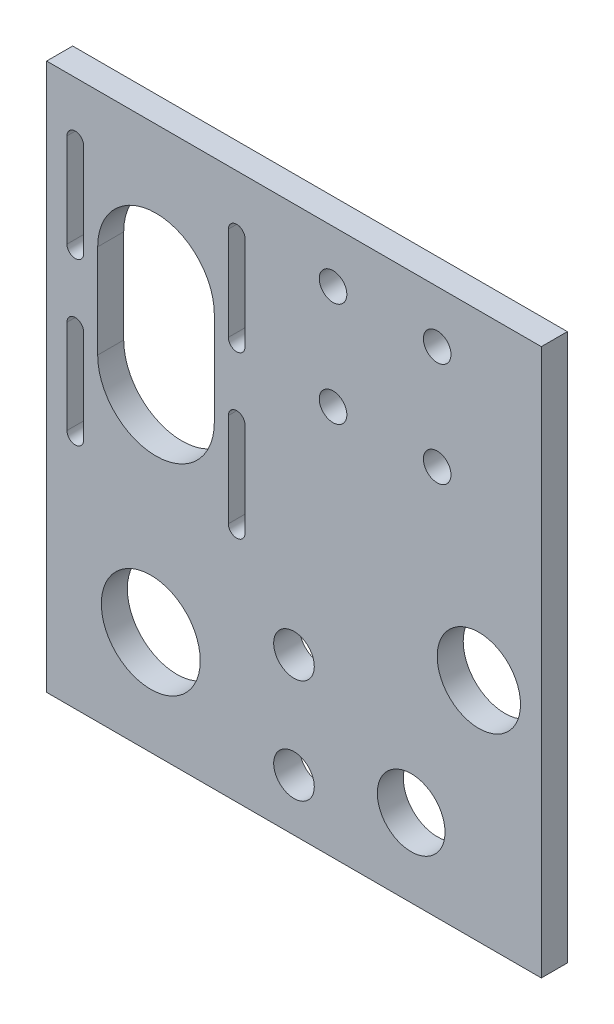
SolidWorks part; units mm, degrees
material "5052-O"
ref_plane "前基準面" through (0, 0, 0) normal (0, 0, 1) x (1, 0, 0)
ref_plane "上基準面" through (0, 0, 0) normal (0, 1, 0) x (1, 0, 0)
ref_plane "右基準面" through (0, 0, 0) normal (1, 0, 0) x (0, 0, -1)
sketch "草圖1" plane through (0, 0, 0) normal (0, 0, 1) x (1, 0, 0)
  line L1 (-47.5, -37.5) -> (47.5, -37.5)
  line L2 (-47.5, -37.5) -> (-47.5, 37.5)
  line L3 (-47.5, 37.5) -> (47.5, 37.5)
  line L4 (47.5, -37.5) -> (47.5, 37.5)
  line L5 (-47.5, -37.5) -> (47.5, 37.5) construction
  line L6 (-47.5, 37.5) -> (47.5, -37.5) construction
  point P0 (0, 0)
  dimension "D1" = 95
  dimension "D2" = 75
extrude "填料-伸長1" add sketch "草圖1" along normal blind 5
hole_wizard "M5 餘隙孔1" positions "草圖2" profile "草圖3" hole size "M5" standard "Ansi Metric" end condition through all
sketch "草圖2" plane through (0, 0, 5) normal (0, 0, 1) x (1, 0, 0)
  line L3 (7.5, 7.5) -> (27.5, 7.5) construction
  line L4 (7.5, 7.5) -> (7.5, 27.5) construction
  line L5 (7.5, 27.5) -> (27.5, 27.5) construction
  line L6 (27.5, 7.5) -> (27.5, 27.5) construction
  line L7 (7.5, 7.5) -> (27.5, 27.5) construction
  line L8 (7.5, 27.5) -> (27.5, 7.5) construction
  line L11 (47.5, 37.5) -> (-47.5, 37.5) construction
  line L12 (47.5, -37.5) -> (47.5, 37.5) construction
  point P6 (27.5, 27.5)
  point P15 (7.5, 7.5)
  point P16 (7.5, 27.5)
  point P17 (27.5, 7.5)
  point P35 (17.5, 17.5)
  dimension "D1" = 20
  dimension "D2" = 20
  dimension "D3" = 20
  dimension "D4" = 20
sketch "草圖3" plane through (27.5, 27.5, 5) normal (1, 0, 0) x (0, -1, 0)
  line L0 (0, 0) -> (0, 5)
  line L1 (0, 5) -> (2.65, 5)
  line L2 (2.65, 5) -> (2.65, 0)
  line L5 (2.65, 0) -> (0, 0)
  line L11 (0, -6.35) -> (0, 107.95) construction
  dimension "貫穿孔直徑" = 5.3
  dimension "貫穿孔深度" = 5
sketch "草圖6" plane through (0, 0, 5) normal (0, 0, 1) x (1, 0, 0)
  line L0 (47.5, 37.5) -> (-47.5, 37.5) construction
  line L2 (-26.5, -6.5) -> (-26.5, 11.5) construction
  line L3 (-37.7, -6.5) -> (-37.7, 11.5)
  line L4 (-15.3, -6.5) -> (-15.3, 11.5)
  line L6 (-42, 27) -> (-42, 9) construction
  line L7 (-42, -4) -> (-11, -4) construction
  line L8 (-42, -4) -> (-42, 27) construction
  line L9 (-42, 27) -> (-11, 27) construction
  line L10 (-11, -4) -> (-11, 27) construction
  line L11 (-42, -4) -> (-11, 27) construction
  line L12 (-42, 27) -> (-11, -4) construction
  line L13 (-40.4, 27) -> (-40.4, 9)
  line L14 (-43.6, 27) -> (-43.6, 9)
  line L15 (-11, 27) -> (-11, 9) construction
  line L16 (-9.4, 27) -> (-9.4, 9)
  line L17 (-12.6, 27) -> (-12.6, 9)
  line L18 (-11, -4) -> (-11, -22) construction
  line L19 (-9.4, -4) -> (-9.4, -22)
  line L20 (-12.6, -4) -> (-12.6, -22)
  line L21 (-42, -4) -> (-42, -22) construction
  line L22 (-40.4, -4) -> (-40.4, -22)
  line L23 (-43.6, -4) -> (-43.6, -22)
  line L25 (-47.5, 37.5) -> (-47.5, -37.5) construction
  arc A0 (-37.7, -6.5) -> (-15.3, -6.5) centre (-26.5, -6.5) ccw
  arc A1 (-15.3, 11.5) -> (-37.7, 11.5) centre (-26.5, 11.5) ccw
  arc A2 (-40.4, 27) -> (-43.6, 27) centre (-42, 27) ccw
  arc A3 (-43.6, 9) -> (-40.4, 9) centre (-42, 9) ccw
  arc A4 (-9.4, 27) -> (-12.6, 27) centre (-11, 27) ccw
  arc A5 (-12.6, 9) -> (-9.4, 9) centre (-11, 9) ccw
  arc A6 (-9.4, -4) -> (-12.6, -4) centre (-11, -4) ccw
  arc A7 (-12.6, -22) -> (-9.4, -22) centre (-11, -22) ccw
  arc A8 (-40.4, -4) -> (-43.6, -4) centre (-42, -4) ccw
  arc A9 (-43.6, -22) -> (-40.4, -22) centre (-42, -22) ccw
  point P6 (-26.5, 2.5)
  point P13 (-26.5, 11.5)
  point P18 (-42, 18)
  point P24 (-11, 18)
  point P30 (-11, -13)
  point P36 (-42, -13)
  dimension "D3" = 11.2
  dimension "D7" = 1.6
  dimension "D1" = 18
  dimension "D2" = 21
  dimension "D4" = 35
  dimension "D5" = 31
  dimension "D6" = 31
extrude "除料-伸長2" cut sketch "草圖6" against normal through all
sketch "草圖4" plane through (0, 0, 5) normal (0, 0, 1) x (1, 0, 0)
  circle A0 centre (35.5, -24) radius 8
  circle A1 centre (27.5, 7.5) radius 2.65 construction
  dimension "D3" = 16
  dimension "D1" = 31.5
  dimension "D2" = 8
extrude "除料-伸長3" cut sketch "草圖4" against normal up to next
sketch "草圖7" plane through (0, -37.5, 0) normal (0, -1, 0) x (-1, 0, 0)
  line L1 (47.5, 0) -> (-47.5, 0)
  line L2 (47.5, 0) -> (47.5, -5)
  line L3 (47.5, -5) -> (-47.5, -5)
  line L4 (-47.5, 0) -> (-47.5, -5)
extrude "填料-伸長2" add sketch "草圖7" along normal blind 30
sketch "草圖8" plane through (0, 0, 5) normal (0, 0, 1) x (1, 0, 0)
  line L0 (47.5, -67.5) -> (-47.5, -67.5) construction
  line L1 (-47.5, 37.5) -> (-47.5, -67.5) construction
  circle A0 centre (-27.5, -47.5) radius 9.5
  dimension "D1" = 19
  dimension "D2" = 20
  dimension "D3" = 20
extrude "除料-伸長4" cut sketch "草圖8" against normal up to next
sketch "草圖9" plane through (0, 0, 5) normal (0, 0, 1) x (1, 0, 0)
  line L0 (47.5, -67.5) -> (-47.5, -67.5) construction
  circle A0 centre (0, -37.5) radius 3.9
  circle A1 centre (0, -57.5) radius 3.9
  point P4 (4.8435, -57.0096)
  point P5 (0, 0)
  point P6 (0.1014, -58.8873)
  point P7 (0, 0)
  point P9 (0, -35.4244)
  dimension "D2" = 7.8
  dimension "D3" = 7.8
  dimension "D4" = 10
  dimension "D1" = 20
extrude "除料-伸長5" cut sketch "草圖9" against normal up to next
sketch "草圖10" plane through (0, 0, 5) normal (0, 0, 1) x (1, 0, 0)
  line L0 (47.5, -67.5) -> (47.5, 37.5) construction
  line L1 (47.5, -67.5) -> (-47.5, -67.5) construction
  circle A0 centre (22.5, -52.5) radius 6.5
  dimension "D2" = 15
  dimension "D3" = 13
  dimension "D1" = 25
extrude "除料-伸長6" cut sketch "草圖10" against normal up to next
